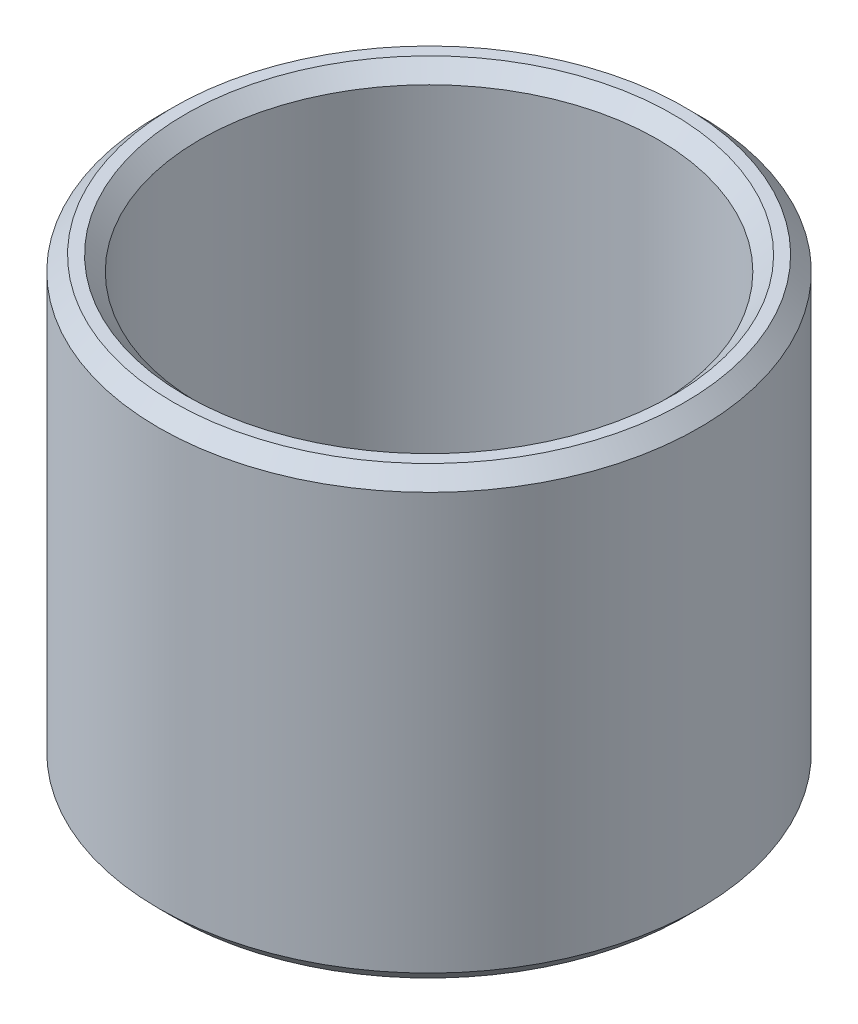
SolidWorks part; units mm, degrees
ref_plane "Front Plane" through (0, 0, 0) normal (0, 0, 1) x (1, 0, 0)
ref_plane "Top Plane" through (0, 0, 0) normal (0, 1, 0) x (1, 0, 0)
ref_plane "Right Plane" through (0, 0, 0) normal (1, 0, 0) x (0, 0, -1)
sketch "Sketch1" plane through (0, 0, 0) normal (0, 1, 0) x (1, 0, 0)
  circle A0 centre (0, 0) radius 57.5
  dimension "SLEEVE_OD" = 115
extrude "Boss-Extrude1" add sketch "Sketch1" along normal blind 94.785
sketch "Sketch2" plane through (0, 0, 0) normal (0, 1, 0) x (1, 0, 0)
  circle A0 centre (0, 0) radius 48.6996
  dimension "BORE_D" = 97.3991
extrude "Cut-Extrude1" cut sketch "Sketch2" along normal through all
chamfer "Chamfer1" distance 3.1185 angle 45 4 edges at (0, 94.785, 48.6996) (0, 0, 48.6996) (0, 0, 57.5) (0, 94.785, 57.5)
